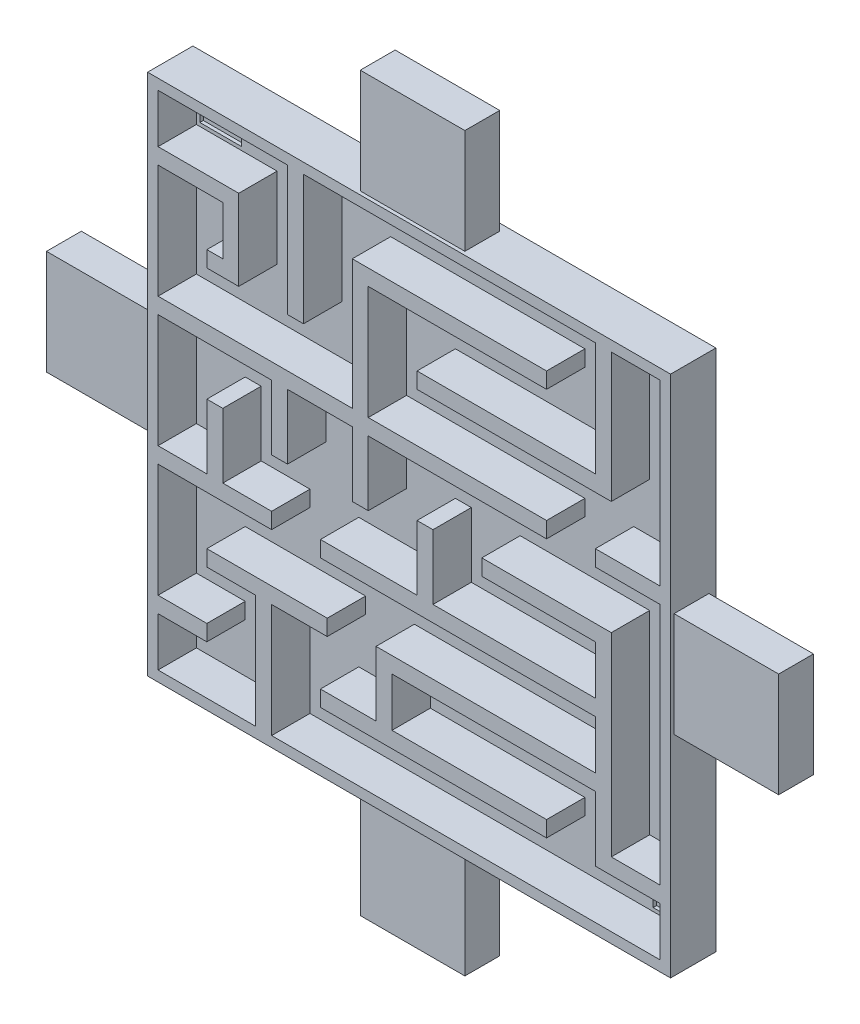
SolidWorks part; units mm, degrees
ref_plane "Front Plane" through (0, 0, 0) normal (0, 0, 1) x (1, 0, 0)
ref_plane "Top Plane" through (0, 0, 0) normal (0, 1, 0) x (1, 0, 0)
ref_plane "Right Plane" through (0, 0, 0) normal (1, 0, 0) x (0, 0, -1)
sketch "Sketch2" plane through (0, 0, 0) normal (0, 0, 1) x (1, 0, 0)
  line L1 (0, 0) -> (150, 0)
  line L2 (0, 0) -> (0, -150)
  line L3 (0, -150) -> (150, -150)
  line L4 (150, 0) -> (150, -150)
  dimension "D1" = 150
extrude "Boss-Extrude1" add sketch "Sketch2" along normal blind 2
sketch "Sketch3" plane through (0, 0, 2) normal (0, 0, 1) x (1, 0, 0)
  line L0 (140, -133) -> (140, -128.4286) construction
  line L1 (0, -3) -> (3, -3)
  line L2 (0, -3) -> (0, -150)
  line L3 (0, -150) -> (3, -150)
  line L4 (3, -3) -> (3, -150)
  line L5 (150, -150) -> (150, 0) construction
  line L10 (3, -147) -> (150, -147)
  line L15 (150, -147) -> (147, -147)
  line L16 (150, -147) -> (150, -3)
  line L17 (150, -3) -> (147, -3)
  line L18 (147, -147) -> (147, -3)
  line L19 (3, -147) -> (3, -150)
  line L20 (3, -150) -> (150, -150)
  line L21 (150, -147) -> (150, -150)
  line L22 (0, 0) -> (150, 0)
  line L23 (0, 0) -> (0, -3)
  line L24 (0, -3) -> (150, -3)
  line L25 (150, 0) -> (150, -3)
  line L26 (3, -17) -> (21.5714, -17)
  line L27 (3, -17) -> (3, -21.5714)
  line L28 (3, -21.5714) -> (21.5714, -21.5714)
  line L29 (21.5714, -17) -> (21.5714, -21.5714)
  line L30 (40.1429, -3) -> (44.7143, -3)
  line L31 (40.1429, -3) -> (40.1429, -40.1429)
  line L32 (40.1429, -40.1429) -> (44.7143, -40.1429)
  line L33 (44.7143, -3) -> (44.7143, -40.1429)
  line L34 (21.5714, -17) -> (26.1429, -17)
  line L35 (21.5714, -17) -> (21.5714, -35.5714)
  line L36 (21.5714, -35.5714) -> (26.1429, -35.5714)
  line L37 (26.1429, -17) -> (26.1429, -35.5714)
  line L38 (26.1429, -35.5714) -> (17, -35.5714)
  line L39 (26.1429, -35.5714) -> (26.1429, -40.1429)
  line L40 (26.1429, -40.1429) -> (17, -40.1429)
  line L41 (17, -35.5714) -> (17, -40.1429)
  line L42 (3, -54.1429) -> (114.4286, -54.1429)
  line L43 (3, -54.1429) -> (3, -58.7143)
  line L44 (3, -58.7143) -> (114.4286, -58.7143)
  line L45 (114.4286, -54.1429) -> (114.4286, -58.7143)
  line L46 (58.7143, -54.1429) -> (63.2857, -54.1429)
  line L47 (58.7143, -54.1429) -> (58.7143, -21.5714)
  line L48 (58.7143, -21.5714) -> (63.2857, -21.5714)
  line L49 (63.2857, -54.1429) -> (63.2857, -21.5714)
  line L50 (58.7143, -21.5714) -> (114.4286, -21.5714)
  line L51 (58.7143, -21.5714) -> (58.7143, -17)
  line L52 (58.7143, -17) -> (114.4286, -17)
  line L53 (114.4286, -21.5714) -> (114.4286, -17)
  line L54 (128.4286, -3) -> (133, -3)
  line L55 (128.4286, -3) -> (128.4286, -40.1429)
  line L56 (128.4286, -40.1429) -> (133, -40.1429)
  line L57 (133, -3) -> (133, -40.1429)
  line L66 (128.4286, -54.1429) -> (147, -54.1429)
  line L67 (128.4286, -54.1429) -> (128.4286, -58.7143)
  line L68 (128.4286, -58.7143) -> (147, -58.7143)
  line L69 (147, -54.1429) -> (147, -58.7143)
  line L70 (128.4286, -40.1429) -> (77.2857, -40.1429)
  line L71 (128.4286, -40.1429) -> (128.4286, -35.5714)
  line L72 (128.4286, -35.5714) -> (77.2857, -35.5714)
  line L73 (77.2857, -40.1429) -> (77.2857, -35.5714)
  line L74 (95.8571, -72.7143) -> (128.4286, -72.7143)
  line L75 (95.8571, -72.7143) -> (95.8571, -77.2857)
  line L76 (95.8571, -77.2857) -> (128.4286, -77.2857)
  line L77 (128.4286, -72.7143) -> (128.4286, -77.2857)
  line L78 (128.4286, -72.7143) -> (133, -72.7143)
  line L79 (128.4286, -72.7143) -> (128.4286, -133)
  line L80 (128.4286, -133) -> (133, -133)
  line L81 (133, -72.7143) -> (133, -133)
  line L82 (133, -133) -> (147, -133)
  line L83 (133, -133) -> (133, -128.4286)
  line L84 (133, -128.4286) -> (147, -128.4286)
  line L85 (147, -133) -> (147, -128.4286)
  line L86 (128.4286, -95.8571) -> (49.5714, -95.8571)
  line L87 (128.4286, -95.8571) -> (128.4286, -91.2857)
  line L88 (128.4286, -91.2857) -> (49.5714, -91.2857)
  line L89 (49.5714, -95.8571) -> (49.5714, -91.2857)
  line L90 (77.2857, -91.2857) -> (81.8571, -91.2857)
  line L91 (77.2857, -91.2857) -> (77.2857, -72.7143)
  line L92 (77.2857, -72.7143) -> (81.8571, -72.7143)
  line L93 (81.8571, -91.2857) -> (81.8571, -72.7143)
  line L94 (35.5714, -58.7143) -> (40.1429, -58.7143)
  line L95 (35.5714, -58.7143) -> (35.5714, -77.2857)
  line L96 (35.5714, -77.2857) -> (40.1429, -77.2857)
  line L97 (40.1429, -58.7143) -> (40.1429, -77.2857)
  line L98 (35.5714, -95.8571) -> (3, -95.8571)
  line L99 (35.5714, -95.8571) -> (35.5714, -91.2857)
  line L100 (35.5714, -91.2857) -> (3, -91.2857)
  line L101 (3, -95.8571) -> (3, -91.2857)
  line L102 (17, -91.2857) -> (21.5714, -91.2857)
  line L103 (17, -91.2857) -> (17, -72.7143)
  line L104 (17, -72.7143) -> (21.5714, -72.7143)
  line L105 (21.5714, -91.2857) -> (21.5714, -72.7143)
  line L106 (35.5714, -109.8571) -> (31, -109.8571)
  line L107 (35.5714, -109.8571) -> (35.5714, -147)
  line L108 (35.5714, -147) -> (31, -147)
  line L109 (31, -109.8571) -> (31, -147)
  line L110 (31, -109.8571) -> (17, -109.8571)
  line L111 (31, -109.8571) -> (31, -114.4286)
  line L112 (31, -114.4286) -> (17, -114.4286)
  line L113 (17, -109.8571) -> (17, -114.4286)
  line L114 (3, -128.4286) -> (17, -128.4286)
  line L115 (3, -128.4286) -> (3, -133)
  line L116 (3, -133) -> (17, -133)
  line L117 (17, -128.4286) -> (17, -133)
  line L122 (114.4286, -133) -> (65.5253, -133)
  line L123 (114.4286, -133) -> (114.4286, -128.4286)
  line L124 (114.4286, -128.4286) -> (65.5253, -128.4286)
  line L125 (65.5253, -133) -> (65.5253, -128.4286)
  line L126 (65.5253, -128.4286) -> (70.0967, -128.4286)
  line L127 (65.5253, -128.4286) -> (65.5253, -109.8571)
  line L128 (65.5253, -109.8571) -> (70.0967, -109.8571)
  line L129 (70.0967, -128.4286) -> (70.0967, -109.8571)
  line L130 (70.0967, -109.8571) -> (128.4286, -109.8571)
  line L131 (70.0967, -109.8571) -> (70.0967, -114.4286)
  line L132 (70.0967, -114.4286) -> (128.4286, -114.4286)
  line L133 (128.4286, -109.8571) -> (128.4286, -114.4286)
  line L134 (58.7143, -58.7143) -> (63.2857, -58.7143)
  line L135 (58.7143, -58.7143) -> (58.7143, -77.2857)
  line L136 (58.7143, -77.2857) -> (63.2857, -77.2857)
  line L137 (63.2857, -58.7143) -> (63.2857, -77.2857)
  line L138 (99.2626, -109.8571) -> (99.2626, -114.4286) construction
  line L140 (35.5714, -109.8571) -> (51.5253, -109.8571)
  line L141 (35.5714, -109.8571) -> (35.5714, -114.4286)
  line L142 (35.5714, -114.4286) -> (51.5253, -114.4286)
  line L143 (51.5253, -109.8571) -> (51.5253, -114.4286)
  line L144 (65.5253, -133) -> (49.5714, -133)
  line L145 (65.5253, -133) -> (65.5253, -128.4286)
  line L146 (65.5253, -128.4286) -> (49.5714, -128.4286)
  line L147 (49.5714, -133) -> (49.5714, -128.4286)
  line M25 (0, 0) -> (0, -150)
  line M26 (0, -150) -> (150, -150)
  dimension "D1" = 3
  dimension "D2" = 14
  dimension "D3" = 14
  dimension "D4" = 14
  dimension "D5" = 14
  dimension "D6" = 14
  dimension "D7" = 14
  dimension "D8" = 14
  dimension "D9" = 14
  dimension "D11" = 14
  dimension "D12" = 14
  dimension "D13" = 14
  dimension "D14" = 14
  dimension "D15" = 14
  dimension "D16" = 14
  dimension "D17" = 14
  dimension "D18" = 14
  dimension "D19" = 14
  dimension "D20" = 14
  dimension "D21" = 14
  dimension "D22" = 14
  dimension "D23" = 14
  dimension "D24" = 14
  dimension "D25" = 14
  dimension "D26" = 14
  dimension "D27" = 14
  dimension "D29" = 14
  dimension "D10" = 14
  dimension "D31" = 14
  dimension "D32" = 14
  dimension "D33" = 14
  dimension "D28" = 14
  dimension "D30" = 14
extrude "Boss-Extrude2" add sketch "Sketch3" along normal blind 11 contours L50 L53 L52 L51 L48 | L42 L49 L48 L47 | L73 L70 L55 L72 | L57 L24 L55 L56 | L67 L68 L18 L66 | L81 L78 L77 L79 L80 | L88 L93 L92 L91 | L89 L86 L79 L88 | L99 L100 L4 L98 | L117 L114 L4 L116 | L110 L113 L112 L109 | L129 L132 L79 L130 | L124 L129 L128 L127 | L125 L122 L123 L124 | L4 L1 M25 M26 | L43 L42 L45 L44 | L27 L26 L29 L28 | L35 L34 L37 L36 | L31 L32 L33 L30 | L23 L22 L25 L24 | L18 L17 L16 L15 | L77 L76 L75 L74 | L82 L85 L84 L83 | L135 L136 L137 L134 | L95 L96 L97 L94 | L103 L104 L105 L102 | L109 L108 L107 L106 | L19 L10 L21 L20 | L141 L140 L143 L142 | L145 L144 L147 L146 | L39 L38 L41 L40 region at (1.5, -76.5, 2) region at (130.7143, -21.5714, 2) region at (10, -130.7143, 2) region at (61, -37.8571, 2) region at (102.8571, -37.8571, 2) region at (24, -112.1429, 2) region at (137.7143, -56.4286, 2) region at (19.2857, -93.5714, 2) region at (86.5714, -19.2857, 2) region at (130.7143, -102.8571, 2) region at (99.2626, -112.1429, 2) region at (67.811, -119.1429, 2) region at (89, -93.5714, 2) region at (89.9769, -130.7143, 2) region at (79.5714, -82, 2)
sketch "Sketch4" plane through (0, 0, 2) normal (0, 0, 1) x (1, 0, 0)
  line L1 (16, -16) -> (4, -16)
  line L2 (16, -16) -> (16, -4)
  line L3 (16, -4) -> (4, -4)
  line L4 (4, -16) -> (4, -4)
  line L5 (3, -10) -> (4, -10) construction
  line L6 (3, -3) -> (3, -17) construction
  line L7 (10, -16) -> (10, -17) construction
  line L8 (3, -17) -> (26.1429, -17) construction
  line L9 (140, -133) -> (140, -134) construction
  line L10 (134, -134) -> (146, -134)
  line L11 (134, -134) -> (134, -146)
  line L12 (134, -146) -> (146, -146)
  line L13 (146, -134) -> (146, -146)
  line L15 (146, -140) -> (147, -140) construction
  line L17 (128.4286, -133) -> (147, -133) construction
  line L18 (147, -147) -> (147, -133) construction
  dimension "D1" = 12
  dimension "D2" = 12
extrude "Cut-Extrude1" cut sketch "Sketch4" against normal offset from surface (1 mm away) 1 up to face at (75, -75, 0)
sketch "Sketch5" plane through (0, 0, 2) normal (0, 0, 1) x (1, 0, 0)
  line L0 (3, -147) -> (147, -3) construction
sketch "Sketch6" plane through (0, 0, 2) normal (0, 0, 1) x (1, 0, 0)
  line L0 (4, -4) -> (16, -16) construction
  line L1 (150, 0) -> (150, -150) construction
  line L2 (10, -10) -> (0, -10) construction
  line L3 (0, 0) -> (0, -150) construction
  line L4 (10, -10) -> (10, 0) construction
  line L5 (0, 0) -> (150, 0) construction
  line L6 (60, 0) -> (90, 0)
  line L7 (60, 0) -> (60, 30)
  line L8 (60, 30) -> (90, 30)
  line L9 (90, 0) -> (90, 30)
  line L10 (150, -60) -> (180, -60)
  line L11 (150, -60) -> (150, -90)
  line L12 (150, -90) -> (180, -90)
  line L13 (180, -60) -> (180, -90)
  line L14 (0, -150) -> (150, -150) construction
  line L15 (90, -150) -> (60, -150)
  line L16 (90, -150) -> (90, -180)
  line L17 (90, -180) -> (60, -180)
  line L18 (60, -150) -> (60, -180)
  line L19 (0, -150) -> (60, -180) construction
  line L20 (0, -90) -> (-30, -90)
  line L21 (0, -90) -> (0, -60)
  line L22 (0, -60) -> (-30, -60)
  line L23 (-30, -90) -> (-30, -60)
  line L24 (90, -180) -> (150, -150) construction
  line L25 (-30, -60) -> (0, 0) construction
  line L30 (0, -150) -> (-30, -90) construction
  point P32 (0, 0)
  dimension "D1" = 30
extrude "Boss-Extrude3" add sketch "Sketch6" along normal blind 10
sketch "Sketch8" plane through (0, 0, 0) normal (0, 0, -1) x (-1, 0, 0)
  line L0 (-3, -147) -> (-147, -3) construction
  circle A0 centre (-75, -75) radius 25.3982
sketch "Sketch9" plane through (0, 0, 2) normal (0, 0, 1) x (1, 0, 0)
  line L0 (0, -150) -> (150, -150) construction
  line L1 (0, 0) -> (150, 0) construction
  line L2 (0, 0) -> (0, -150) construction
  circle A0 centre (75, -75) radius 75
equation "\"x\"= 1.4"
equation "\"D25@Sketch3\"=\"x\""
equation "\"D27@Sketch3\"=\"x\""
equation "\"D29@Sketch3\"=\"x\""
equation "\"D24@Sketch3\"=\"x\""
equation "\"D26@Sketch3\"=\"x\""
equation "\"D20@Sketch3\"=\"x\""
equation "\"D21@Sketch3\"=\"x\""
equation "\"D22@Sketch3\"=\"x\""
equation "\"D23@Sketch3\"=\"x\""
equation "\"D19@Sketch3\"=\"x\""
equation "\"D16@Sketch3\"=\"x\""
equation "\"D18@Sketch3\"=\"x\""
equation "\"D17@Sketch3\"=\"x\""
equation "\"D12@Sketch3\"=\"x\""
equation "\"D9@Sketch3\"=\"x\""
equation "\"D15@Sketch3\"=\"x\""
equation "\"D11@Sketch3\"=\"x\""
equation "\"D13@Sketch3\"=\"x\""
equation "\"D2@Sketch3\"=\"x\""
equation "\"D6@Sketch3\"=\"x\""
equation "\"D3@Sketch3\"=\"x\""
equation "\"D5@Sketch3\"=\"x\""
equation "\"D4@Sketch3\"=\"x\""
equation "\"D7@Sketch3\"=\"x\""
equation "\"D8@Sketch3\"=\"x\""
equation "\"D14@Sketch3\"=\"x\""
equation "\"D10@Sketch3\"=\"x\""
equation "\"D31@Sketch3\"=\"x\""
equation "\"D32@Sketch3\"=\"x\""
equation "\"D33@Sketch3\"=\"x\""
equation "\"D28@Sketch3\"=\"x\""
equation "\"D30@Sketch3\"=\"x\""
